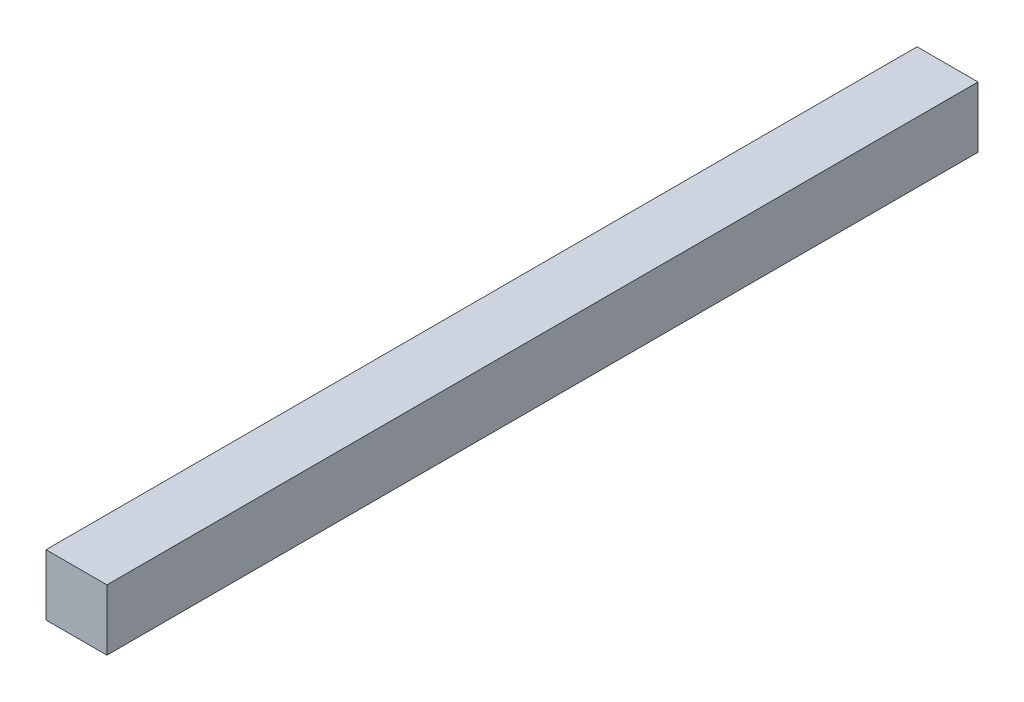
SolidWorks part; units mm, degrees
ref_plane "Płaszczyzna przednia" through (0, 0, 0) normal (0, 0, 1) x (1, 0, 0)
ref_plane "Płaszczyzna górna" through (0, 0, 0) normal (0, 1, 0) x (1, 0, 0)
ref_plane "Płaszczyzna prawa" through (0, 0, 0) normal (1, 0, 0) x (0, 0, -1)
sketch "Szkic1" plane through (0, 0, 0) normal (0, 0, 1) x (1, 0, 0)
  line L1 (-5, -5) -> (5, -5)
  line L2 (-5, -5) -> (-5, 5)
  line L3 (-5, 5) -> (5, 5)
  line L4 (5, -5) -> (5, 5)
  line L5 (-5, -5) -> (5, 5) construction
  line L6 (-5, 5) -> (5, -5) construction
  line L7 (-3.5, -3.5) -> (3.5, -3.5)
  line L8 (-3.5, -3.5) -> (-3.5, 3.5)
  line L9 (-3.5, 3.5) -> (3.5, 3.5)
  line L10 (3.5, -3.5) -> (3.5, 3.5)
  line L11 (-3.5, -3.5) -> (3.5, 3.5) construction
  line L12 (-3.5, 3.5) -> (3.5, -3.5) construction
  point P0 (0, 0)
  point P5 (0, 0)
  dimension "D1" = 10
  dimension "D2" = 7
extrude "Dodanie-wyciągnięcie1" add sketch "Szkic1" along normal blind 143 contours L1 L4 L3 L2 L10 L7 L8 L9 | L2 L3 L4 L1 region at (-4.8586, 0, 0)
